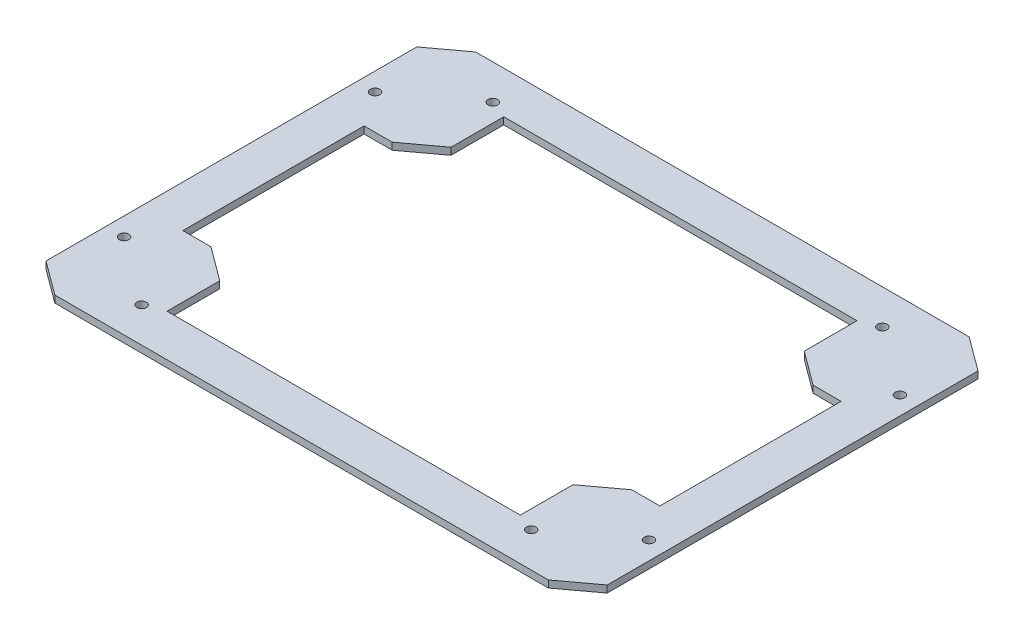
SolidWorks part; units mm, degrees
material "Thornel Mat VMA"
ref_plane "Front Plane" through (0, 0, 0) normal (0, 0, 1) x (1, 0, 0)
ref_plane "Top Plane" through (0, 0, 0) normal (0, 1, 0) x (1, 0, 0)
ref_plane "Right Plane" through (0, 0, 0) normal (1, 0, 0) x (0, 0, -1)
sketch "Sketch1" plane through (0, 0, 0) normal (0, 1, 0) x (1, 0, 0)
  line L0 (-127, 83.9186) -> (-111.6865, 95.25)
  line L1 (-127, -95.25) -> (127, -95.25)
  line L2 (-127, -95.25) -> (-127, 95.25)
  line L3 (-127, 95.25) -> (127, 95.25)
  line L4 (127, -95.25) -> (127, 95.25)
  line L5 (-107.95, 41.011) -> (-107.95, -41.011)
  line L8 (-107.95, 41.011) -> (-95.25, 41.011)
  line L10 (-127, 95.25) -> (127, -95.25) construction
  line L12 (127, 83.9186) -> (111.6865, 95.25)
  line L14 (79.9365, 52.3423) -> (79.9365, 76.2)
  line L15 (95.25, 41.011) -> (79.9365, 52.3423)
  line L16 (107.95, 41.011) -> (95.25, 41.011)
  line L17 (107.95, 41.011) -> (107.95, -41.011)
  line L18 (127, -83.9186) -> (111.6865, -95.25)
  line L19 (107.95, -41.011) -> (95.25, -41.011)
  line L20 (95.25, -41.011) -> (79.9365, -52.3423)
  line L21 (79.9365, -52.3423) -> (79.9365, -76.2)
  line L22 (127, 0) -> (-127, 0) construction
  line L23 (0, -13.6985) -> (0, 95.25) construction
  line L26 (-79.9365, -52.3423) -> (-79.9365, -76.2)
  line L27 (-95.25, 41.011) -> (-127, 83.9186) construction
  line L28 (-95.25, 41.011) -> (-79.9365, 52.3423)
  line L29 (-79.9365, 52.3423) -> (-79.9365, 76.2)
  line L31 (-95.25, -41.011) -> (-79.9365, -52.3423)
  line L32 (-107.95, -41.011) -> (-95.25, -41.011)
  line L33 (-127, -83.9186) -> (-111.6865, -95.25)
  line L34 (-79.9365, 52.3423) -> (-111.6865, 95.25) construction
  line L36 (-79.9365, 76.2) -> (79.9365, 76.2)
  line L37 (38.8318, 76.2) -> (79.9365, 76.2)
  line L38 (-79.9365, -76.2) -> (79.9365, -76.2)
  line L39 (38.1, -76.2) -> (79.9365, -76.2)
  point P0 (0, 0)
  point P1 (0, 0)
  point P14 (0, 0)
  point P22 (0, 76.2)
  point P33 (107.95, 0)
  point P41 (0, 0)
  point P44 (-107.95, 0)
  point P45 (-38.1, 0)
  point P46 (-31.75, 0)
  dimension "D1" = 190.5
  dimension "D2" = 254
  dimension "D3" = 19.05
  dimension "D4" = 19.05
  dimension "D5" = 143.5
  dimension "D6" = 19.05
  dimension "D7" = 12.7
extrude "Boss-Extrude1" add sketch "Sketch1" along normal blind 3.175 contours L2 L1 L4 L3 L8 region at (-117.4547, 0, -87.0321)
sketch "Sketch2" plane through (0, 3.175, 0) normal (0, 1, 0) x (1, 0, 0)
  line L0 (-87.5933, 46.6767) -> (-119.3433, 89.5843) construction
  line L1 (-95.25, 41.011) -> (-79.9365, 52.3423) construction
  line L2 (-127, 83.9186) -> (-111.6865, 95.25) construction
  line L3 (0, 0) -> (0, 95.25) construction
  line L4 (-111.6865, 95.25) -> (111.6865, 95.25) construction
  line L5 (0, 0) -> (-127, 0) construction
  line L6 (-127, -83.9186) -> (-127, 83.9186) construction
  line L7 (-103.4683, 68.1305) -> (-88.1548, 79.4619) construction
  circle A0 centre (-88.1548, 79.4619) radius 2.159
  circle A1 centre (88.1548, 79.4619) radius 2.159
  circle A2 centre (88.1548, -79.4619) radius 2.159
  circle A3 centre (-88.1548, -79.4619) radius 2.159
  circle A4 centre (-118.7817, 56.7991) radius 2.159
  circle A5 centre (118.7817, 56.7991) radius 2.159
  circle A6 centre (-118.7817, -56.7991) radius 2.159
  circle A7 centre (118.7817, -56.7991) radius 2.159
  dimension "D1" = 19.05
extrude "Cut-Extrude1" cut sketch "Sketch2" against normal through all
